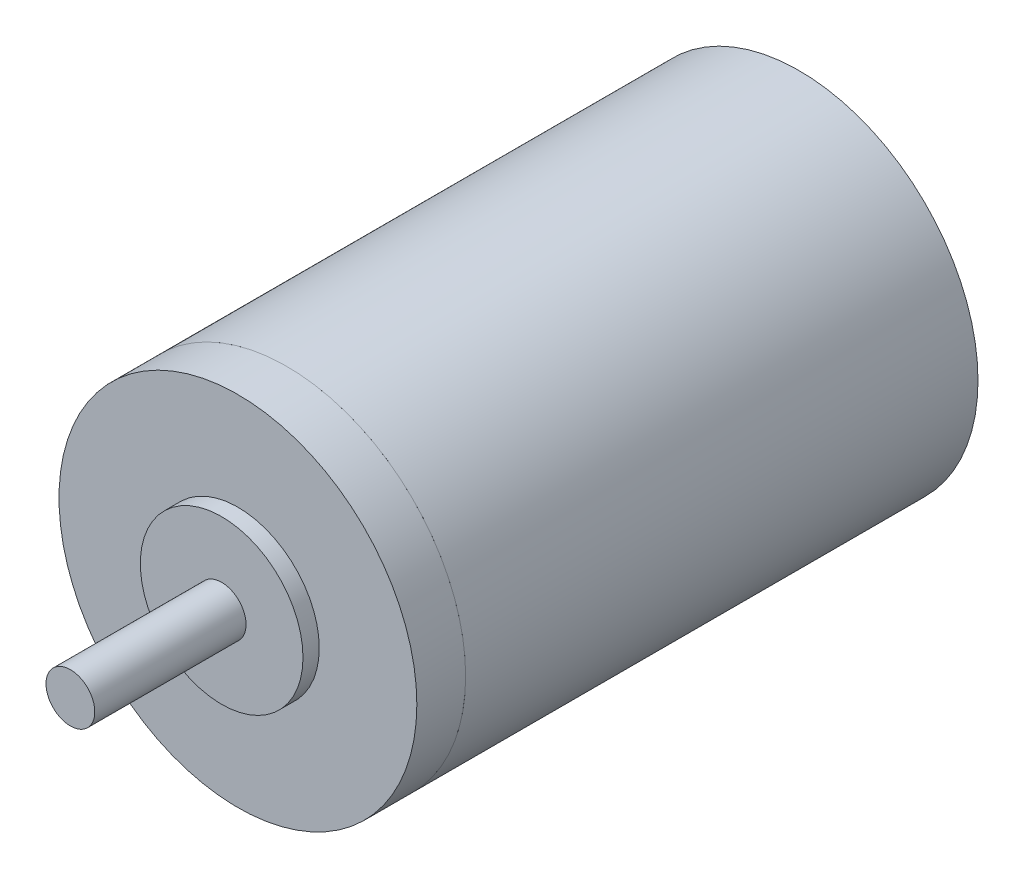
SolidWorks part; units mm, degrees
material "Alloy Steel"
ref_plane "Front Plane" through (0, 0, 0) normal (0, 0, 1) x (1, 0, 0)
ref_plane "Top Plane" through (0, 0, 0) normal (0, 1, 0) x (1, 0, 0)
ref_plane "Right Plane" through (0, 0, 0) normal (1, 0, 0) x (0, 0, -1)
sketch "Sketch1" plane through (0, 0, 0) normal (0, 0, 1) x (1, 0, 0)
  circle A0 centre (0, 0) radius 11
  circle A1 centre (0, 0) radius 5
  circle A2 centre (0, 0) radius 1.5
  dimension "D1" = 22
  dimension "D2" = 10
  dimension "D3" = 3
extrude "Body" add sketch "Sketch1" against normal blind 34.5 contours A0 A1 | A1 A2 | A2 region at (-10.6889, 0, 0) region at (-4.8586, 0, 0) region at (0, 0, 0)
extrude "Collar" add sketch "Sketch1<3>" along normal blind 1 contours A1 A2 | A2 region at (-4.8586, 0, 0) region at (0, 0, 0)
sketch "Sketch1<3>" plane through (0, 0, 0) normal (0, 0, 1) x (1, 0, 0) same geometry as "Sketch1"
extrude "Shaft" add sketch "Sketch1<4>" along normal blind 10.3 contours A2
sketch "Sketch1<4>" plane through (0, 0, 0) normal (0, 0, 1) x (1, 0, 0) same geometry as "Sketch1"
sketch "Sketch2" plane through (0, 0, 0) normal (0, 0, 1) x (1, 0, 0)
  circle A0 centre (0, 0) radius 11
  circle A1 centre (0, 0) radius 11 construction
  circle A2 centre (0, 0) radius 10.5
  dimension "D1" = 0.5
extrude "Cap Ring" cut sketch "Sketch2" against normal blind 0.001 from offset 3 offset against normal yes
